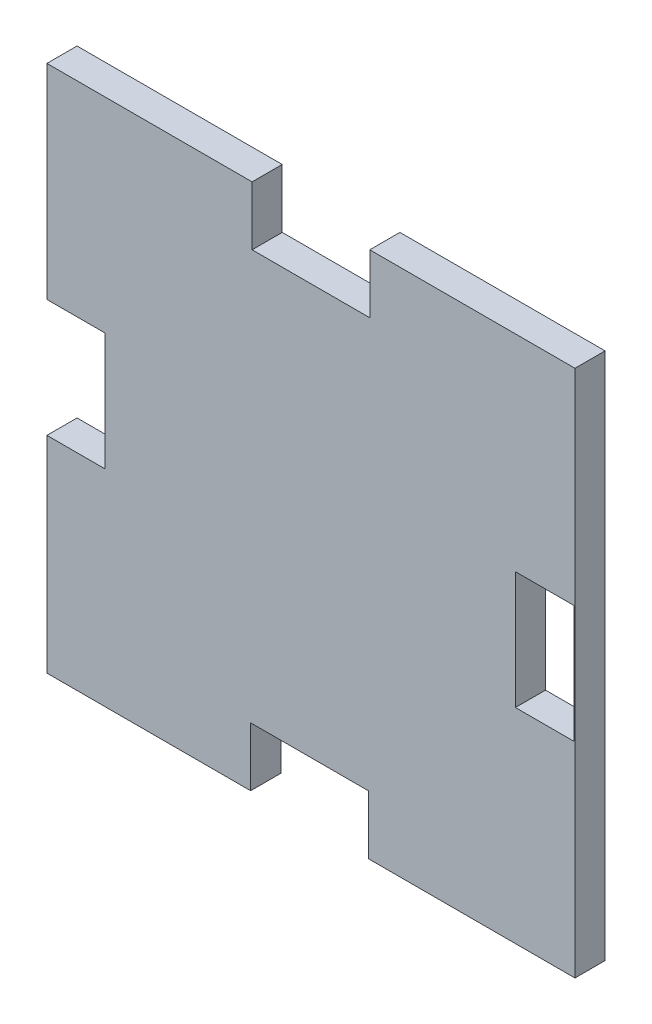
SolidWorks part; units mm, degrees
ref_plane "Front Plane" through (0, 0, 0) normal (0, 0, 1) x (1, 0, 0)
ref_plane "Top Plane" through (0, 0, 0) normal (0, 1, 0) x (1, 0, 0)
ref_plane "Right Plane" through (0, 0, 0) normal (1, 0, 0) x (0, 0, -1)
sketch "Sketch1" plane through (0, 0, 0) normal (0, 0, 1) x (1, 0, 0)
  line L2 (1.1204, 62.1576) -> (1.1204, 32.2376)
  line L5 (31.0404, 2.3176) -> (60.9604, 2.3176)
  line L6 (90.8804, 32.2376) -> (90.8804, 62.1576)
  line L8 (1.1204, 92.0776) -> (1.1204, 62.1576)
  line L9 (60.9604, 92.0776) -> (31.0404, 92.0776)
  line L12 (1.1204, 2.3176) -> (1.1204, 32.2376)
  line L15 (1.1204, 92.0776) -> (31.0404, 92.0776)
  line L19 (90.8804, 92.0776) -> (60.9604, 92.0776)
  line L22 (90.8804, 92.0776) -> (90.8804, 62.1576)
  line L27 (90.8804, 2.3176) -> (60.9604, 2.3176)
  line L28 (90.8804, 32.2376) -> (90.8804, 2.3176)
  line L33 (1.1204, 2.3176) -> (31.0404, 2.3176)
  dimension "D1" = 89.76
  dimension "D2" = 89.76
extrude "Boss-Extrude1" add sketch "Sketch1" along normal blind 5.12
sketch "Sketch2" plane through (0, 0, 5.12) normal (0, 0, 1) x (1, 0, 0)
  line L0 (1.1204, 47.1976) -> (50001.1204, 47.1976) construction
  line L1 (1.1204, 2.3176) -> (90.8804, 2.3176) construction
  line L2 (1.1204, 2.3176) -> (35.7493, 2.3176) construction
  line L3 (55.7493, 2.3176) -> (90.3781, 2.3176) construction
  line L4 (1.1204, 92.0776) -> (1.1204, 2.3176) construction
  line L5 (90.8804, 2.3176) -> (90.8804, 92.0776) construction
  line L6 (45.7493, 2.3176) -> (185.6341, 50002.122) construction
  line L7 (90.8804, 92.0776) -> (1.1204, 92.0776) construction
  line L8 (0.9948, 57.3232) -> (10.9948, 57.3232)
  line L9 (10.9948, 57.3232) -> (10.9948, 37.3232)
  line L10 (0.9948, 37.3232) -> (10.9948, 37.3232)
  line L11 (0.9948, 57.3232) -> (0.9948, 37.3232)
  line L12 (56.0004, 92.0776) -> (56.0004, 82.0776)
  line L13 (56.0004, 82.0776) -> (36.0004, 82.0776)
  line L14 (36.0004, 92.0776) -> (36.0004, 82.0776)
  line L15 (56.0004, 92.0776) -> (36.0004, 92.0776)
  line L16 (90.7548, 37.0721) -> (80.7548, 37.0721)
  line L17 (35.7493, 2.3176) -> (55.7493, 2.3176)
  line L18 (35.7493, 2.3176) -> (35.7493, 12.3176)
  line L19 (35.7493, 12.3176) -> (55.7493, 12.3176)
  line L20 (55.7493, 2.3176) -> (55.7493, 12.3176)
  line L21 (80.7548, 37.0721) -> (80.7548, 57.0721)
  line L22 (90.7548, 57.0721) -> (80.7548, 57.0721)
  line L23 (90.7548, 37.0721) -> (90.7548, 57.0721)
  point P10 (1.1204, 47.1976)
  point P13 (90.8804, 47.1976)
  point P17 (45.7493, 2.3176)
  point P25 (46.0004, 92.0776)
  point P26 (45.8748, 47.1976)
  dimension "D1" = 0
  dimension "D2" = 10
  dimension "D3" = 20
  dimension "D4" = 4
extrude "Cut-Extrude1" cut sketch "Sketch2" against normal through all
equation "\"mdf\"=\"mdf@fmv1.assembly\""
equation "\"D1@Boss-Extrude1\"=\"mdf\""
equation "\"D1@Sketch1\" = 100-2*\"mdf\""
equation "\"D2@Sketch1\" = 100-2*\"mdf\""
